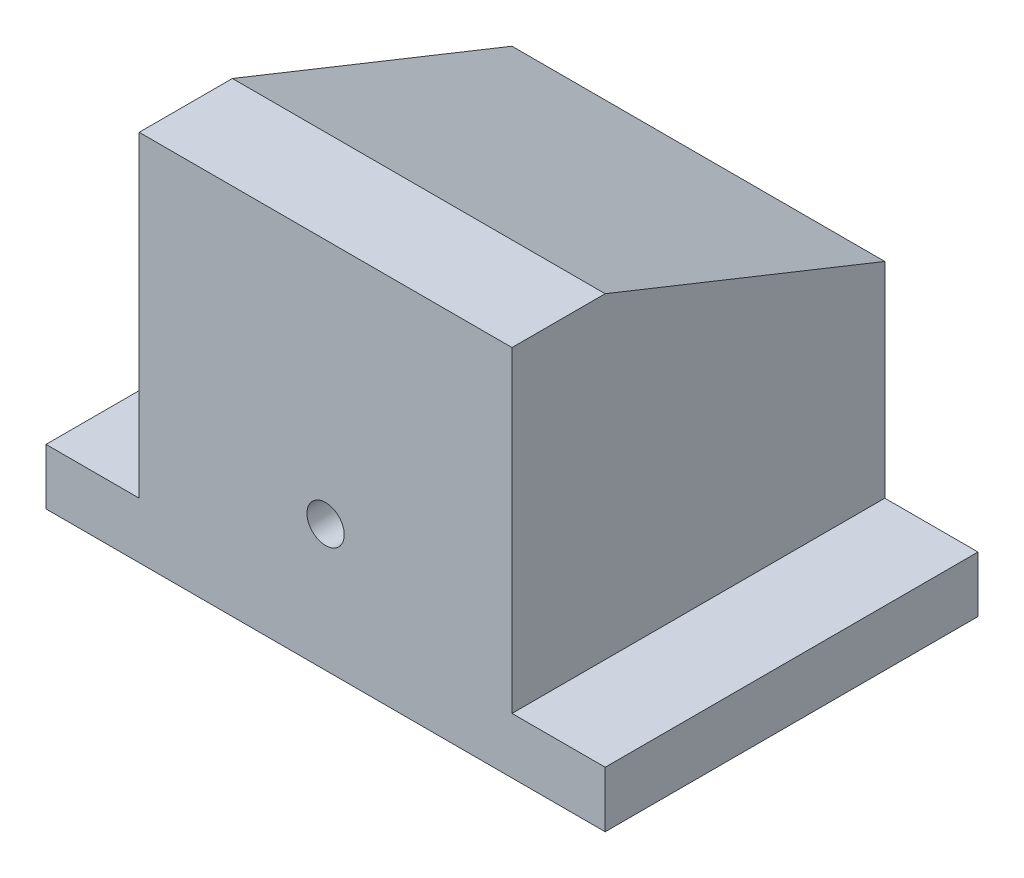
SolidWorks part; units mm, degrees
ref_plane "Ebene vorne" through (0, 0, 0) normal (0, 0, 1) x (1, 0, 0)
ref_plane "Ebene oben" through (0, 0, 0) normal (0, 1, 0) x (1, 0, 0)
ref_plane "Ebene rechts" through (0, 0, 0) normal (1, 0, 0) x (0, 0, -1)
sketch "Sketch1" plane through (0, 0, 0) normal (0, 1, 0) x (1, 0, 0)
  line L1 (0, 0) -> (20, 0)
  line L2 (0, 0) -> (0, 20)
  line L3 (0, 20) -> (20, 20)
  line L4 (20, 0) -> (20, 20)
  dimension "D1" = 20
  dimension "D2" = 20
extrude "Boss-Extrude1" add sketch "Sketch1" along normal blind 20
fillet "Chamfer1" radius 6 1 edges at (10, 20, -20) profile chamfer first distance on face at (10, 10, -20)
sketch "Sketch2" plane through (0, 0, 0) normal (0, -1, 0) x (1, 0, 0)
  line L0 (20, -10) -> (0, -10) construction
  line L1 (20, 0) -> (20, -20) construction
  line L2 (0, -20) -> (0, 0) construction
  circle A0 centre (10, -10) radius 7.6
  dimension "D1" = 15.2
extrude "Cut-Extrude1" cut sketch "Sketch2" against normal blind 12
sketch "Sketch3" plane through (0, 0, -20) normal (0, 0, -1) x (-1, 0, 0)
  line L0 (-10, 0) -> (-10, 14) construction
  line L1 (-20, 0) -> (0, 0) construction
  line L2 (0, 14) -> (-20, 14) construction
  line L3 (-17.6, 12) -> (-2.4, 12) construction
  line L4 (-17.6, 12) -> (-2.4, 12) construction
  circle A0 centre (-10, 6.8) radius 1
  dimension "D1" = 2
  dimension "D2" = 5.2
extrude "Cut-Extrude2" cut sketch "Sketch3" against normal up to surface (20 mm away) up to face at (10, 10, 0)
sketch "Sketch4" plane through (0, 0, 0) normal (0, -1, 0) x (-1, 0, 0)
  line L0 (-10, 20) -> (-10, 0) construction
  line L11 (-20, 0) -> (-25, 0)
  line L12 (-20, 0) -> (-20, 20)
  line L13 (-20, 20) -> (-25, 20)
  line L14 (-25, 0) -> (-25, 20)
  line L15 (-20, 20) -> (0, 20) construction
  line L16 (0, 0) -> (-20, 0) construction
  line L17 (5, 0) -> (5, 20)
  line L18 (0, 20) -> (5, 20)
  line L19 (0, 0) -> (0, 20)
  line L20 (0, 0) -> (5, 0)
  dimension "D1" = 30
extrude "Boss-Extrude2" add sketch "Sketch4" against normal blind 3
